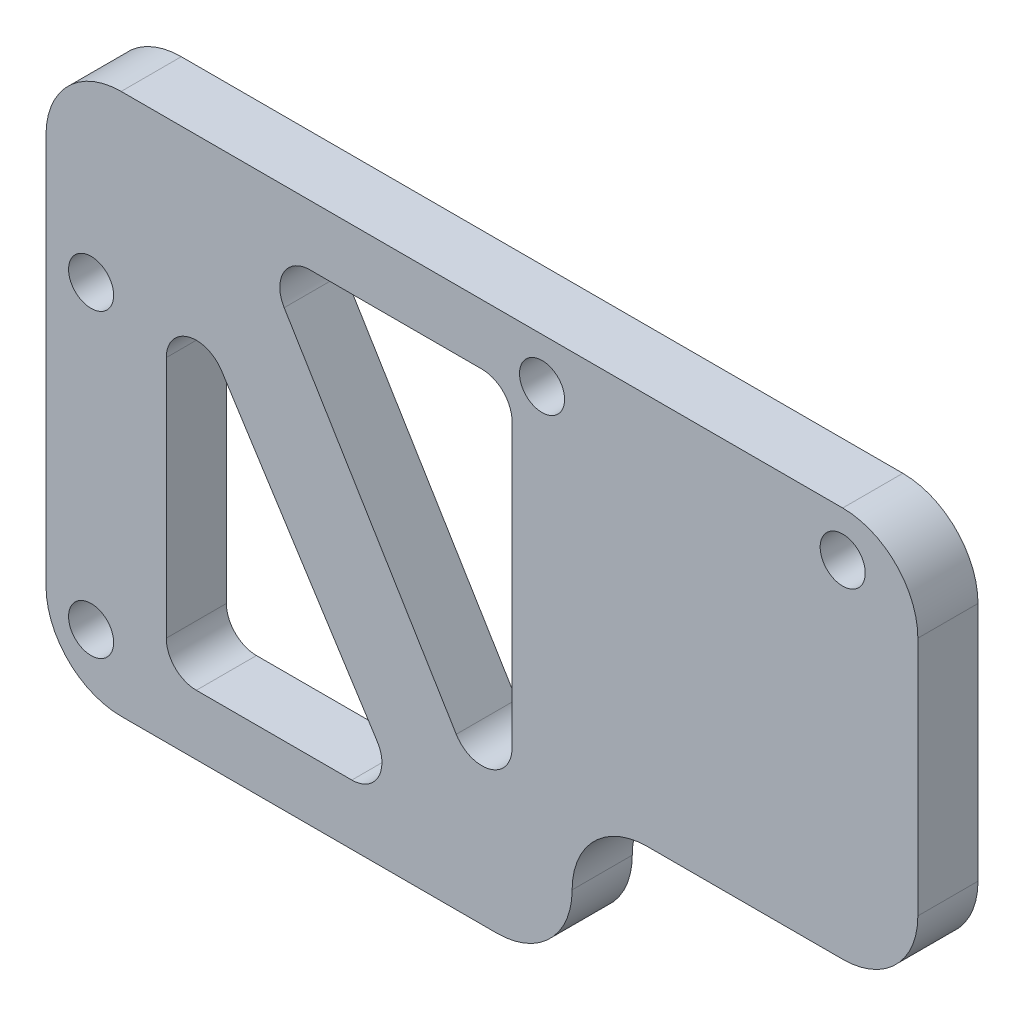
SolidWorks part; units mm, degrees
ref_plane "前视基准面" through (0, 0, 0) normal (0, 0, 1) x (1, 0, 0)
ref_plane "上视基准面" through (0, 0, 0) normal (0, 1, 0) x (1, 0, 0)
ref_plane "右视基准面" through (0, 0, 0) normal (1, 0, 0) x (0, 0, -1)
sketch "草图1" plane through (0, 0, 0) normal (0, 0, 1) x (1, 0, 0)
  line L6 (0, 0) -> (0, 36)
  line L7 (0, 36) -> (35, 36)
  line L9 (135, 16.4475) -> (135, 0)
  line L10 (135, 0) -> (0, 0)
  line L12 (35, 36) -> (135, 36)
  line L13 (135, 36) -> (135, 16.4475)
  dimension "D1" = 36
  dimension "D2" = 135
  dimension "D3" = 35
extrude "凸台-拉伸2" add sketch "草图1" along normal blind 4
sketch "草图2" plane through (0, 0, 4) normal (0, 0, 1) x (1, 0, 0)
  line L0 (0, 36) -> (0, 0) construction
  line L1 (0, 0) -> (135, 0) construction
  circle A0 centre (3, 4) radius 1.5
  circle A1 centre (3, 24) radius 1.5
  dimension "D1" = 3
  dimension "D5" = 3
  dimension "D2" = 3
  dimension "D3" = 4
  dimension "D4" = 20
  dimension "D6" = 3
extrude "切除-拉伸1" cut sketch "草图2" against normal blind 10
sketch "草图4" plane through (0, 0, 4) normal (0, 0, 1) x (1, 0, 0)
  line L0 (135, 10) -> (35, 10)
  line L2 (35, 10) -> (35, 0)
  line L3 (0, 0) -> (135, 0) construction
  line L4 (35, 0) -> (135, 0)
  line L5 (135, 0) -> (135, 10)
  dimension "D1" = 100
  dimension "D2" = 10
extrude "切除-拉伸2" cut sketch "草图4" against normal blind 10
fillet "圆角1" radius 5 6 edges at (35, 10, 2) (135, 10, 2) (135, 36, 2) (0, 36, 2) (0, 0, 2) (35, 0, 2)
sketch "草图5" plane through (0, 0, 4) normal (0, 0, 1) x (1, 0, 0)
  line L0 (135, 36) -> (97.5, 36) construction
  line L2 (97.5, 36) -> (97.5, 33) construction
  line L3 (97.5, 33) -> (53, 33) construction
  line L4 (135, 15) -> (135, 31) construction
  line L5 (130, 36) -> (5, 36) construction
  circle A0 centre (97.5, 33) radius 1.5
  circle A1 centre (53, 33) radius 1.5
  circle A2 centre (77.5, 33) radius 1.5
  dimension "D4" = 3
  dimension "D6" = 3
  dimension "D8" = 3
  dimension "D1" = 37.5
  dimension "D2" = 90
  dimension "D3" = 3
  dimension "D5" = 44.5
  dimension "D7" = 24.5
extrude "切除-拉伸3" cut sketch "草图5" against normal blind 6
sketch "草图7" plane through (0, 0, 4) normal (0, 0, 1) x (1, 0, 0)
  line L0 (0, 30.97) -> (-4, 30.97)
  line L1 (0, 31) -> (0, 5) construction
  line L2 (-4, 30.97) -> (-4, 5.03)
  line L3 (-4, 5.03) -> (0, 5.03)
  line L4 (0, 5.03) -> (0, 30.97)
  line L5 (5, 0) -> (30, 0) construction
  line L6 (130, 36) -> (5, 36) construction
  dimension "D1" = 5.03
  dimension "D2" = 5.03
  dimension "D3" = 4
extrude "凸台-拉伸3" add sketch "草图7" against normal blind 2
fillet "圆角5" radius 1 2 edges at (-4, 5.03, 3) (-4, 30.97, 3)
sketch "草图9" plane through (0, 0, 4) normal (0, 0, 1) x (1, 0, 0)
  line L0 (130, 10) -> (40, 10) construction
  line L1 (135, 15) -> (135, 31) construction
  circle A0 centre (110, 17) radius 1.5
  dimension "D1" = 3
  dimension "D2" = 7
  dimension "D3" = 25
extrude "切除-拉伸6" cut sketch "草图9" against normal blind 10
sketch "草图11" plane through (0, 0, 4) normal (0, 0, 1) x (1, 0, 0)
  line L0 (8, 29) -> (8, 4)
  line L1 (8, 4) -> (24, 4)
  line L2 (24, 4) -> (8, 29)
  line L3 (5, 0) -> (30, 0) construction
  line L5 (-4, 29.97) -> (-4, 6.03) construction
  line L6 (14, 32) -> (31, 32)
  line L7 (31, 32) -> (31, 4)
  line L8 (31, 4) -> (14, 32)
  line L14 (130, 36) -> (5, 36) construction
  line L15 (39, 29) -> (39, 18)
  line L18 (129, 29) -> (39, 29)
  line L22 (39, 18) -> (129, 29)
  line L23 (39, 18) -> (84, 29)
  line L24 (64.2681, 21.0883) -> (96.6341, 29)
  dimension "D1" = 4
  dimension "D2" = 12
  dimension "D3" = 16
  dimension "D4" = 25
  dimension "D5" = 4
  dimension "D6" = 35
  dimension "D7" = 17
  dimension "D8" = 7
  dimension "D9" = 8
  dimension "D10" = 11
  dimension "D11" = 90
  dimension "D12" = 3
sketch "草图13" plane through (0, 0, 4) normal (0, 0, 1) x (1, 0, 0)
  line L0 (33, 33) -> (53, 33) construction
  circle A0 centre (33, 33) radius 1.5
  circle A1 centre (53, 33) radius 1.5 construction
  circle A2 centre (53, 33) radius 1.5 construction
  dimension "D2" = 3
  dimension "D1" = 20
extrude "切除-拉伸8" cut sketch "草图13" against normal blind 10 contours A0
extrude "切除-拉伸9" cut sketch "草图11" along direction (0, 0, -1) on the side against the normal up to surface (4 mm away) contours L8 L7 L6 | L1 L2 L0 region at (13.3333, 12.3333, 4) region at (25.3333, 22.6667, 4) up to face at (31.5, 33, 0)
fillet "圆角9" radius 2 6 edges at (31, 32, 2) (31, 4, 2) (14, 32, 2) (24, 4, 2) (8, 4, 2) (8, 29, 2)
sketch "草图15" plane through (0, 0, 4) normal (0, 0, 1) x (1, 0, 0)
  line L0 (0, 5.03) -> (0, 30.97)
  line L1 (0, 30.97) -> (-4, 30.97)
  line L2 (-4, 30.97) -> (-4, 5.03)
  line L3 (-4, 5.03) -> (0, 5.03)
  line L4 (-4, 29.97) -> (-4, 6.03) construction
extrude "切除-拉伸12" cut sketch "草图15" against normal blind 10
sketch "草图16" plane through (0, 0, 4) normal (0, 0, 1) x (1, 0, 0)
  line L0 (58, 36) -> (58, 10)
  line L1 (130, 36) -> (5, 36) construction
  line L2 (130, 10) -> (40, 10) construction
  line L3 (58, 10) -> (135, 10)
  line L4 (135, 10) -> (135, 36)
  line L5 (135, 36) -> (58, 36)
  line L6 (135, 15) -> (135, 31) construction
  circle A0 centre (53, 33) radius 1.5 construction
  dimension "D1" = 5
extrude "切除-拉伸13" cut sketch "草图16" against normal blind 10
fillet "圆角10" radius 5 2 edges at (58, 10, 2) (58, 36, 2)
